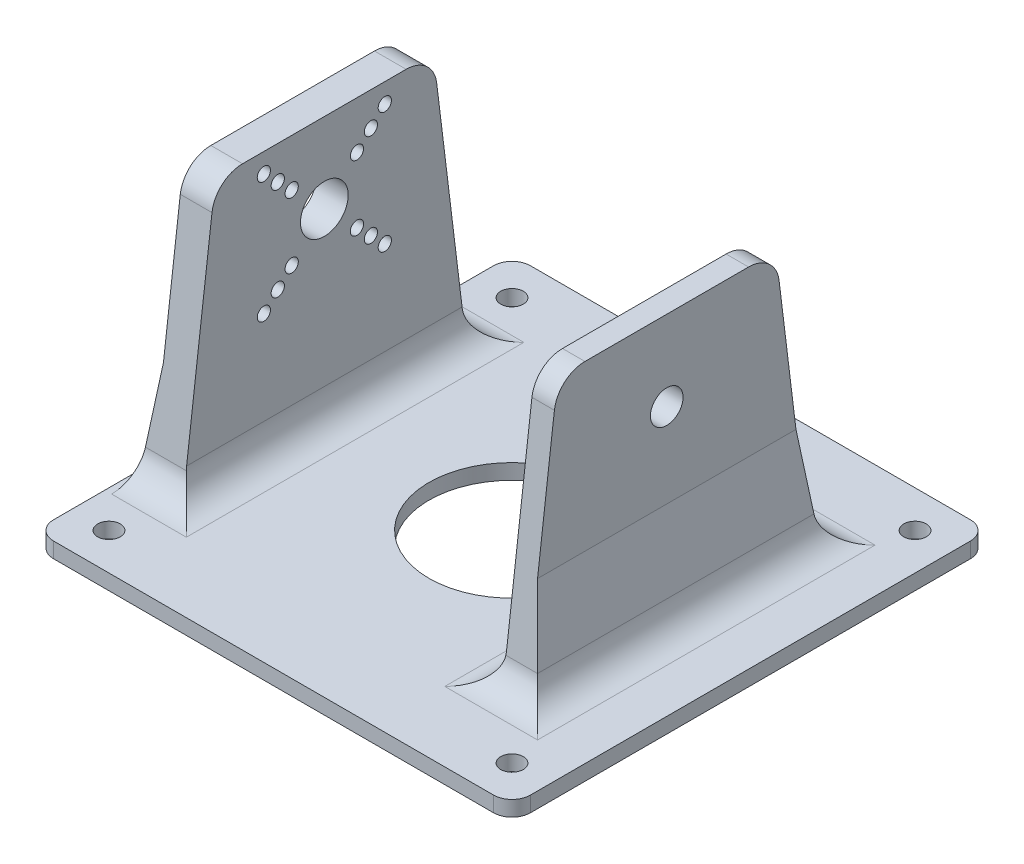
SolidWorks part; units mm, degrees
ref_plane "Front Plane" through (0, 0, 0) normal (0, 0, 1) x (1, 0, 0)
ref_plane "Top Plane" through (0, 0, 0) normal (0, 1, 0) x (1, 0, 0)
ref_plane "Right Plane" through (0, 0, 0) normal (1, 0, 0) x (0, 0, -1)
sketch "Sketch1" plane through (0, 0, 0) normal (0, 1, 0) x (1, 0, 0)
  line L0 (-38.75, -38.75) -> (38.75, -38.75)
  line L1 (-38.75, -38.75) -> (-38.75, 38.75)
  line L2 (-38.75, 38.75) -> (38.75, 38.75)
  line L3 (38.75, -38.75) -> (38.75, 38.75)
  line L4 (-38.75, -38.75) -> (38.75, 38.75) construction
  line L5 (-38.75, 38.75) -> (38.75, -38.75) construction
  circle A0 centre (0, 0) radius 46.3155 construction
  circle A1 centre (32.75, 32.75) radius 1.83
  circle A2 centre (32.75, -32.75) radius 1.83
  circle A3 centre (-32.75, -32.75) radius 1.83
  circle A4 centre (-32.75, 32.75) radius 1.83
  circle A5 centre (0, 0) radius 13.5
  circle A6 centre (0, 0) radius 56.5 construction
  point P12 (0, 0)
  dimension "D2" = 3.66
  dimension "D4" = 27
  dimension "D5" = 113
  dimension "D1" = 65.5
  dimension "D3" = 6
extrude "Boss-Extrude1" add sketch "Sketch1" along normal blind 2.5
fillet "Fillet1" radius 3 4 edges at (38.75, 1.25, -38.75) (38.75, 1.25, 38.75) (-38.75, 1.25, -38.75) (-38.75, 1.25, 38.75)
sketch "Sketch2" plane through (0, 2.5, 0) normal (0, 1, 0) x (1, 0, 0)
  line L0 (0, 0) -> (20, 0) construction
  line L1 (-35.65, 16) -> (-30.5, 16)
  line L2 (-35.65, 16) -> (-35.65, -16)
  line L3 (-35.65, -16) -> (-30.5, -16)
  line L4 (-30.5, 16) -> (-30.5, -16)
  line L5 (20, 16) -> (25.15, 16) construction
  line L6 (20, 16) -> (20, -16) construction
  line L7 (20, -16) -> (25.15, -16) construction
  line L8 (25.15, 16) -> (25.15, -16)
  line L9 (21.5, -16) -> (21.5, 16)
  line L10 (21.5, 16) -> (25.15, 16)
  line L11 (21.5, -16) -> (25.15, -16)
  dimension "D1" = 50.5
  dimension "D2" = 20
  dimension "D3" = 5.15
  dimension "D4" = 32
  dimension "D5" = 1.5
extrude "Boss-Extrude2" add sketch "Sketch2" along normal blind 43
sketch "Sketch3" plane through (-35.65, 0, 0) normal (-1, 0, 0) x (0, 0, 1)
  line L0 (-5.3033, 37.8033) -> (0, 32.5) construction
  line L1 (16, 45.5) -> (16, 2.5) construction
  line L2 (16, 45.5) -> (16, 2.5) construction
  line L3 (-16, 45.5) -> (16, 45.5) construction
  circle A0 centre (0, 32.5) radius 3.875
  circle A1 centre (-5.3033, 37.8033) radius 1.075
  circle A15 centre (5.3033, 37.8033) radius 1.075
  circle A18 centre (5.3033, 27.1967) radius 1.075
  circle A21 centre (-5.3033, 27.1967) radius 1.075
  circle A24 centre (-7.566, 40.066) radius 1.075
  circle A25 centre (-9.8288, 42.3288) radius 1.075
  circle A26 centre (9.8288, 42.3288) radius 1.075
  circle A27 centre (7.566, 40.066) radius 1.075
  circle A28 centre (9.8288, 22.6712) radius 1.075
  circle A29 centre (7.566, 24.934) radius 1.075
  circle A30 centre (-9.8288, 22.6712) radius 1.075
  circle A31 centre (-7.566, 24.934) radius 1.075
  point P28 (0, 32.5)
  point P30 (0, 32.5)
  point P31 (0, 32.5)
  dimension "D1" = 7.75
  dimension "D2" = 2.15
  dimension "D3" = 3.2
  dimension "D4" = 7.5
  dimension "D6" = 3
  dimension "D8" = 13
  dimension "D5" = 4
  dimension "D7" = 4
extrude "Cut-Extrude1" cut sketch "Sketch3" against normal blind 10
sketch "Sketch4" plane through (25.15, 0, 0) normal (1, 0, 0) x (0, 0, -1)
  circle A0 centre (0, 32.5) radius 2.65
  circle A1 centre (0, 32.5) radius 3.875 construction
  circle A2 centre (0, 32.5) radius 3.875 construction
  dimension "D1" = 5.3
extrude "Cut-Extrude2" cut sketch "Sketch4" against normal blind 10
sketch "Sketch5" plane through (21.5, 0, 0) normal (-1, 0, 0) x (0, 0, 1)
  circle A0 centre (0, 32.5) radius 2.65 construction
  circle A1 centre (0, 32.5) radius 3.875 construction
  circle A2 centre (0, 32.5) radius 2.65
  circle A3 centre (0, 32.5) radius 3.875
extrude "Boss-Extrude3" add sketch "Sketch5" along normal blind 1.5
chamfer "Chamfer1" distance 1.5 angle 45 1 edges at (21.5, 32.5, -3.875)
chamfer "Chamfer2" distance 7 angle 83 4 edges at (23.325, 2.5, 16) (-33.075, 2.5, 16) (-33.075, 2.5, -16) (23.325, 2.5, -16) first distance on face at (-33.075, 2.5, 0)
chamfer "Chamfer3" distance 2 angle 83 2 edges at (-35.65, 2.5, 0) (25.15, 2.5, 0) first distance on face at (-33.075, 2.5, 0)
fillet "Fillet2" radius 5 11 edges at (24.325, 2.5, 23) (-34.075, 2.5, 23) (-30.5, 2.5, 0) (-34.075, 2.5, -23) (21.5, 2.5, 0) (24.325, 2.5, -23) (23.325, 45.5, -17.7203) (-33.075, 45.5, -17.7203) (-33.075, 45.5, 17.7203) (23.325, 45.5, 17.7203) (27.15, 2.5, 0)
